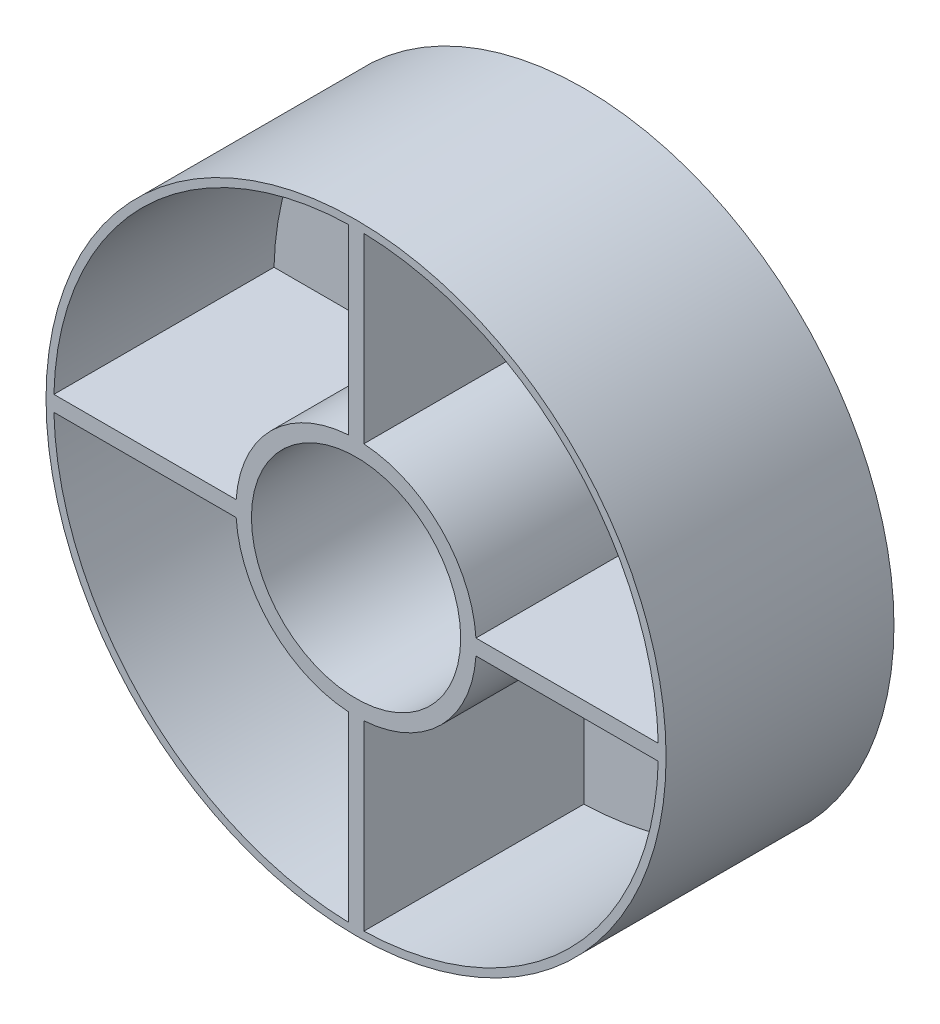
SolidWorks part; units mm, degrees
ref_plane "Front Plane" through (0, 0, 0) normal (0, 0, 1) x (1, 0, 0)
ref_plane "Top Plane" through (0, 0, 0) normal (0, 1, 0) x (1, 0, 0)
ref_plane "Right Plane" through (0, 0, 0) normal (1, 0, 0) x (0, 0, -1)
sketch "Sketch1" plane through (0, 0, 0) normal (0, 0, 1) x (1, 0, 0)
  line L1 (1.5, 11) -> (-1.5, 11)
  line L2 (2.5, 10) -> (2.5, 5)
  line L3 (2.5, 5) -> (-2.5, 5)
  line L4 (-2.5, 10) -> (-2.5, 5)
  line L5 (2.5, 11) -> (-2.5, 5) construction
  line L6 (2.5, 5) -> (-2.5, 11) construction
  circle A0 centre (0, 0) radius 200
  circle A1 centre (0, 0) radius 67.5
  circle A2 centre (0, 0) radius 25
  circle A3 centre (0, 0) radius 77.5
  circle A4 centre (0, 0) radius 8
  arc A5 (2.5, 10) -> (1.5, 11) centre (1.5, 10) ccw
  arc A6 (-2.5, 10) -> (-1.5, 11) centre (-1.5, 10) cw
  circle A7 centre (0, 0) radius 195
  point P7 (0, 8)
  dimension "D1" = 400
  dimension "D2" = 135
  dimension "D3" = 50
  dimension "D4" = 155
  dimension "D5" = 16
  dimension "D8" = 1
  dimension "D9" = 390
  dimension "D6" = 6
  dimension "D7" = 5
extrude "Boss-Extrude1" add sketch "Sketch1" along normal blind 5 contours A7 A3 | A1 A2 region at (-65.5908, 0, 0) region at (-189.4846, 0, 0)
extrude "Boss-Extrude2" add sketch "Sketch1<4>" along normal blind 147 contours A0 A7 region at (-199.4343, 0, 0)
sketch "Sketch1<4>" plane through (0, 0, 0) normal (0, 0, 1) x (1, 0, 0) same geometry as "Sketch1"
extrude "Boss-Extrude3" add sketch "Sketch1<5>" along normal blind 147 contours A3 A1 region at (-75.308, 0, 0)
sketch "Sketch1<5>" plane through (0, 0, 0) normal (0, 0, 1) x (1, 0, 0) same geometry as "Sketch1"
extrude "Boss-Extrude4" add sketch "Sketch1<6>" along normal blind 25 contours A2 L4 A6 L1 A5 L2 A4 region at (-24.2929, 0, 0)
sketch "Sketch1<6>" plane through (0, 0, 0) normal (0, 0, 1) x (1, 0, 0) same geometry as "Sketch1"
extrude "Boss-Extrude5" add sketch "Sketch1<7>" along normal blind 7 contours L4 A4 L2 L3 | L2 A4 L4 L3 | A6 L4 A4 L2 A5 L1 region at (0, 9.3937, 0) region at (0, -0.4943, 0) region at (0, 6.4364, 0)
sketch "Sketch1<7>" plane through (0, 0, 0) normal (0, 0, 1) x (1, 0, 0) same geometry as "Sketch1"
hole_wizard "CBORE for M5 Hex Head Bolt1" positions "Sketch2" profile "Sketch3" counterbore size "M5" standard "ISO" end condition through all
sketch "Sketch2" plane through (0, 0, 0) normal (0, 0, -1) x (-1, 0, 0)
  point P0 (0, 0)
sketch "Sketch3" plane through (0, 0, 0) normal (1, 0, 0) x (0, 1, 0)
  line L0 (0, 0) -> (0, 147)
  line L1 (0, 147) -> (2.9, 147)
  line L3 (2.9, 147) -> (2.9, 3.5)
  line L4 (2.9, 3.5) -> (6.119, 3.5)
  line L5 (6.119, 3.5) -> (6.119, 0)
  line L7 (6.119, 0) -> (0, 0)
  line L11 (0, -6.35) -> (0, 107.95) construction
  dimension "Thru Hole Dia." = 5.8
  dimension "Thru Hole Depth" = 147
  dimension "C'Bore Dia." = 12.238
  dimension "C'Bore Depth" = 3.5
ref_plane "Plane1" through (0, 0, 147) normal (0, 0, 1) x (1, 0, 0)
sketch "Sketch4" plane through (0, 0, 147) normal (0, 0, 1) x (1, 0, 0)
  line L0 (0, 197.4071) -> (0, 77.5)
  line L1 (0, -77.5) -> (0, -197.6514)
  line L2 (77.5, 0) -> (197.9895, 0)
  line L3 (-77.5, 0) -> (-197.0456, 0)
  circle A2 centre (0, 0) radius 77.5 construction
  circle A3 centre (0, 0) radius 77.5 construction
rib "Rib1" sketch "Sketch4" sketch "Sketch4" thickness 10 extrusion direction normal to sketch draft on no parameters "D1"=10
ref_plane "Plane2" through (0, 0, 5) normal (0, 0, 1) x (1, 0, 0)
sketch "Sketch5" plane through (0, 0, 5) normal (0, 0, 1) x (1, 0, 0)
  circle A0 centre (0, 0) radius 57.5
  circle A1 centre (0, 0) radius 70
  dimension "D1" = 115
extrude "Boss-Extrude6" add sketch "Sketch5" along normal blind 29
